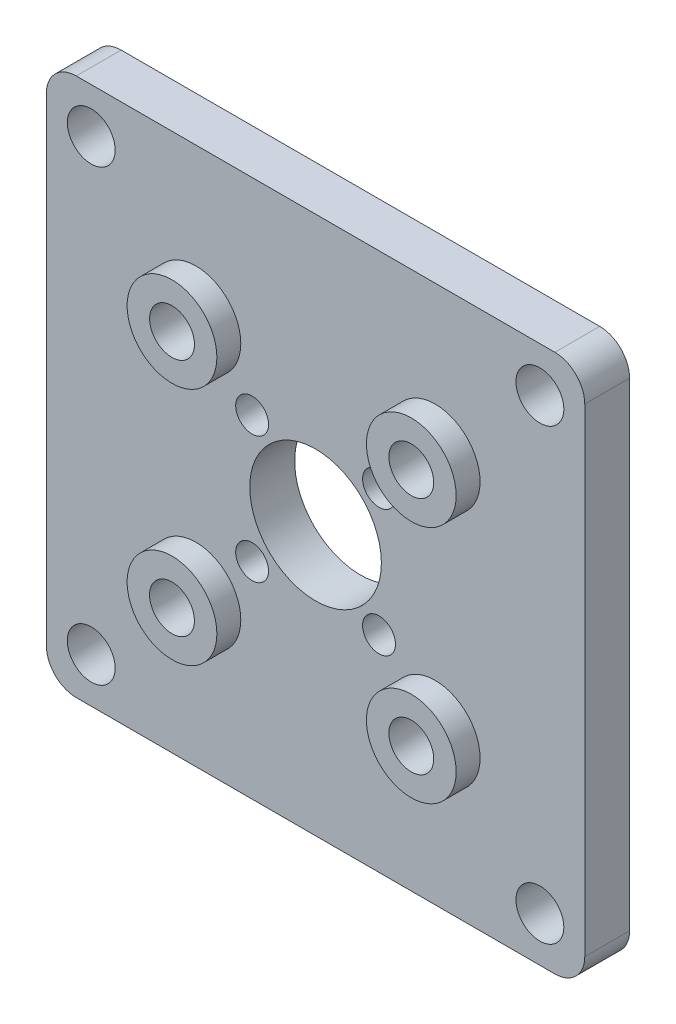
SolidWorks part; units mm, degrees
ref_plane "Plan de face" through (0, 0, 0) normal (0, 0, 1) x (1, 0, 0)
ref_plane "Plan de dessus" through (0, 0, 0) normal (0, 1, 0) x (1, 0, 0)
ref_plane "Plan de droite" through (0, 0, 0) normal (1, 0, 0) x (0, 0, -1)
sketch "Esquisse1" plane through (0, 0, 0) normal (0, 0, 1) x (1, 0, 0)
  line L0 (0, 6) -> (0, 0) construction
  line L1 (0, 0) -> (-4.2426, 4.2426) construction
  line L2 (0, 18) -> (0, 0) construction
  line L3 (18, -18) -> (-18, -18)
  line L4 (18, -18) -> (18, 18)
  line L5 (18, 18) -> (-18, 18)
  line L6 (-18, -18) -> (-18, 18)
  line L7 (18, -18) -> (-18, 18) construction
  line L8 (18, 18) -> (-18, -18) construction
  line L9 (0, 0) -> (18, 0) construction
  circle A0 centre (0, 0) radius 6 construction
  circle A1 centre (-4.2426, 4.2426) radius 1.1
  circle A2 centre (4.2426, 4.2426) radius 1.1
  circle A3 centre (4.2426, -4.2426) radius 1.1
  circle A4 centre (-4.2426, -4.2426) radius 1.1
  circle A5 centre (0, 0) radius 4.4
  circle A6 centre (-15, 15) radius 1.6
  circle A7 centre (0, 0) radius 15 construction
  circle A8 centre (15, 15) radius 1.6
  circle A9 centre (15, -15) radius 1.6
  circle A10 centre (-15, -15) radius 1.6
  point P14 (0, 0)
  dimension "D1" = 12
  dimension "D4" = 2.2
  dimension "D5" = 8.8
  dimension "D9" = 3.2
  dimension "D10" = 30
  dimension "D2" = 45
  dimension "D6" = 36
  dimension "D7" = 3
  dimension "D8" = 3
  dimension "D3" = 4
extrude "Boss.-Extru.1" add sketch "Esquisse1" along normal blind 3
sketch "Esquisse2" plane through (0, 0, 3) normal (0, 0, 1) x (1, 0, 0)
  line L1 (8, -8) -> (-8, -8) construction
  line L2 (8, -8) -> (8, 8) construction
  line L3 (8, 8) -> (-8, 8) construction
  line L4 (-8, -8) -> (-8, 8) construction
  line L5 (8, -8) -> (-8, 8) construction
  line L6 (8, 8) -> (-8, -8) construction
  circle A0 centre (-8, 8) radius 3
  circle A1 centre (8, 8) radius 3
  circle A2 centre (8, -8) radius 3
  circle A3 centre (-8, -8) radius 3
  point P0 (0, 0)
  dimension "D1" = 6
  dimension "D2" = 16
  dimension "D3" = 16
extrude "Boss.-Extru.2" add sketch "Esquisse2" along normal blind 1.6
sketch "Esquisse3" plane through (0, 0, 4.6) normal (0, 0, 1) x (1, 0, 0)
  line L0 (0, 17.8842) -> (0, 0) construction
  line L1 (0, 0) -> (17.8818, 0) construction
  circle A0 centre (-8, 8) radius 1.5
  circle A1 centre (-8, 8) radius 3 construction
  circle A2 centre (8, 8) radius 1.5
  circle A3 centre (8, -8) radius 1.5
  circle A4 centre (-8, -8) radius 1.5
  dimension "D1" = 3
extrude "Enlèv. mat.-Extru.1" cut sketch "Esquisse3" against normal through all
fillet "Congé1" radius 2 4 edges at (-18, 18, 1.5) (-18, -18, 1.5) (18, -18, 1.5) (18, 18, 1.5)
